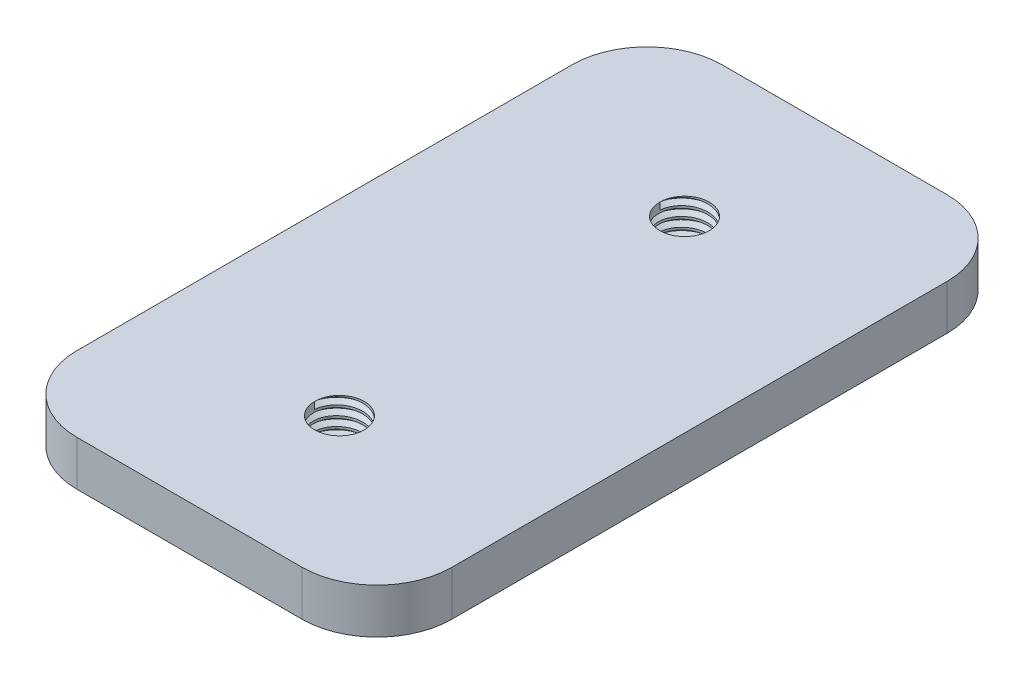
SolidWorks part; units mm, degrees
material "Plain Carbon Steel"
ref_plane "Front Plane" through (0, 0, 0) normal (0, 0, 1) x (1, 0, 0)
ref_plane "Top Plane" through (0, 0, 0) normal (0, 1, 0) x (1, 0, 0)
ref_plane "Right Plane" through (0, 0, 0) normal (1, 0, 0) x (0, 0, -1)
sketch "Sketch1" plane through (0, 0, 0) normal (0, 0, 1) x (1, 0, 0)
  line L0 (-120.7437, 100) -> (120.7056, 0) construction
  line L1 (-120.7056, 0) -> (120.7437, 100) construction
  line L2 (0.0191, 50) -> (0.0191, 0) construction
  line L3 (-120.7056, 0) -> (120.7056, 0) construction
  line L5 (-24.9809, 25) -> (25.0191, 25)
  line L6 (-24.9809, 25) -> (-24.9809, 19)
  line L7 (-24.9809, 19) -> (25.0191, 19)
  line L8 (25.0191, 25) -> (25.0191, 19)
  line L9 (-24.9809, 25) -> (25.0191, 19) construction
  line L10 (-24.9809, 19) -> (25.0191, 25) construction
  point P12 (0.0191, 50)
  point P17 (0.0191, 22)
  dimension "D1" = 6
  dimension "D2" = 50
  dimension "D3" = 25
extrude "Boss-Extrude1" add sketch "Sketch1" along normal blind 40 and the other way blind 46
sketch "Sketch2" plane through (0, 25, 0) normal (0, 1, 0) x (1, 0, 0)
  line L0 (0.0191, -40) -> (0.0191, 46) construction
  line L1 (25.0191, -40) -> (-24.9809, -40) construction
  line L2 (25.0191, 46) -> (-24.9809, 46) construction
  line L3 (0.0191, 3) -> (-24.9809, 3) construction
  line L4 (-24.9809, 46) -> (-24.9809, -40) construction
  circle A0 centre (0.0191, -20) radius 3.3
  circle A1 centre (0.0191, 26) radius 3.3
  dimension "D1" = 6.6
  dimension "D2" = 46
extrude "Cut-Extrude1" cut sketch "Sketch2" against normal through all
fillet "Fillet1" radius 10 4 edges at (25.0191, 22, -46) (-24.9809, 22, -46) (-24.9809, 22, 40) (25.0191, 22, 40)
thread "Thread1" pitch 1.25 method cut profile "Thread Profile1" start angle 0, offset 0, length 10, pitch 1.25, diameter 6.6
ref_plane "Plane1" through (-3.2809, 25, -26) normal (0, 0, 1) x (-1, 0, 0)
sketch "Thread Profile1" plane through (-3.2809, 25, -26) normal (0, 0, 1) x (-1, 0, 0)
  line L0 (0, 0) -> (0, 1.25) construction
  line L1 (0, 0) -> (0.6766, 0.3906)
  line L2 (0.6766, 0.3906) -> (0.6766, 0.5469)
  line L3 (0.6766, 0.5469) -> (0, 0.9375)
  line L4 (0.6766, 0.4687) -> (0, 0.4687) construction
  line L11 (0, 0) -> (0, 0.9375)
  point P2 (0, 0)
  dimension "Pitch" = 1.25
  dimension "Profile_Angle" = 60
  dimension "Profile_Land" = 0.1562
  dimension "Profile_Height" = 0.6766
thread "Thread2" pitch 1.25 method cut profile "Thread Profile2" start angle 0, offset 0, length 10, pitch 1.25, diameter 6.6
ref_plane "Plane2" through (-3.2809, 25, 20) normal (0, 0, 1) x (-1, 0, 0)
sketch "Thread Profile2" plane through (-3.2809, 25, 20) normal (0, 0, 1) x (-1, 0, 0)
  line L0 (0, 0) -> (0, 1.25) construction
  line L1 (0, 0) -> (0.6766, 0.3906)
  line L2 (0.6766, 0.3906) -> (0.6766, 0.5469)
  line L3 (0.6766, 0.5469) -> (0, 0.9375)
  line L4 (0.6766, 0.4687) -> (0, 0.4687) construction
  line L11 (0, 0) -> (0, 0.9375)
  point P2 (0, 0)
  dimension "Pitch" = 1.25
  dimension "Profile_Angle" = 60
  dimension "Profile_Land" = 0.1562
  dimension "Profile_Height" = 0.6766
